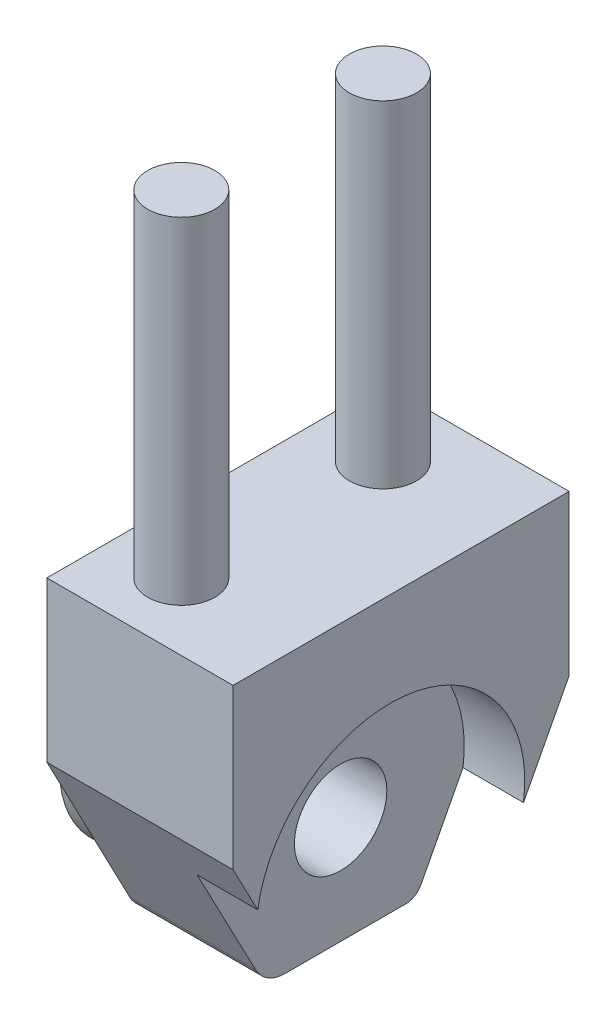
SolidWorks part; units mm, degrees
material "3.0205 (EN-AW 1200)"
ref_plane "Plan de face" through (0, 0, 0) normal (0, 0, 1) x (1, 0, 0)
ref_plane "Plan de dessus" through (0, 0, 0) normal (0, 1, 0) x (1, 0, 0)
ref_plane "Plan de droite" through (0, 0, 0) normal (1, 0, 0) x (0, 0, -1)
sketch "Esquisse1" plane through (0, 0, 0) normal (0, 1, 0) x (1, 0, 0)
  line L1 (15.8141, 19.6321) -> (37.9741, 19.6321)
  line L2 (15.8141, 19.6321) -> (15.8141, -20.3679)
  line L3 (15.8141, -20.3679) -> (37.9741, -20.3679)
  line L4 (37.9741, 19.6321) -> (37.9741, -20.3679)
  dimension "D1" = 40
  dimension "D2" = 22.16
extrude "Boss.-Extru.1" add sketch "Esquisse1" along normal blind 40
chamfer "Chanfrein1" distance 11 distance2 21 1 edges at (26.8941, 0, 20.3679) first distance on face at (26.8941, 0, 0.3679)
chamfer "Chanfrein2" distance 11 distance2 21 1 edges at (26.8941, 0, -19.6321) first distance on face at (26.8941, 0, -5.1321)
fillet "Congé1" radius 4 1 edges at (26.8941, 0, 9.3679)
sketch "Esquisse2" plane through (0, 40, 0) normal (0, 1, 0) x (1, 0, 0)
  line L1 (15.8141, 19.6321) -> (15.8141, -20.3679) construction
  line L2 (15.8141, -20.3679) -> (37.9741, -20.3679) construction
  line L4 (37.9741, 19.6321) -> (15.8141, 19.6321) construction
  circle A0 centre (23.8141, -12.3679) radius 4
  circle A1 centre (23.8141, 11.6321) radius 4
  dimension "D1" = 8
  dimension "D4" = 8
  dimension "D2" = 8
  dimension "D3" = 8
  dimension "D5" = 8
  dimension "D6" = 8
extrude "Boss.-Extru.2" add sketch "Esquisse2" along normal blind 40 contours A1
extrude "Boss.-Extru.3" add sketch "Esquisse2<3>" along normal blind 40
sketch "Esquisse2<3>" plane through (0, 40, 0) normal (0, 1, 0) x (1, 0, 0) same geometry as "Esquisse2"
sketch "Esquisse3" plane through (15.8141, 0, 0) normal (-1, 0, 0) x (0, 0, 1)
  line L0 (-8.6321, 0) -> (6.9476, 0) construction
  line L2 (-19.6321, 40) -> (-19.6321, 21) construction
  circle A0 centre (0.3679, 13.5) radius 12.5
  dimension "D1" = 25
  dimension "D2" = 13.5
  dimension "D3" = 20
extrude "Boss.-Extru.4" add sketch "Esquisse3" along normal blind 6
sketch "Esquisse4" plane through (37.9741, 0, 0) normal (1, 0, 0) x (0, 0, -1)
  line L0 (-20.3679, 40) -> (19.6321, 40) construction
  circle A0 centre (-1.6508, 12.8) radius 16
  dimension "D1" = 32
  dimension "D2" = 27.2
extrude "Enlèv. mat.-Extru.1" cut sketch "Esquisse4" against normal blind 7.2
sketch "Esquisse6" plane through (30.7741, 0, 0) normal (1, 0, 0) x (0, 0, -1)
  line L1 (0.8273, 4.7453) -> (12.9159, 4.7453)
  line L2 (0.8273, 4.7453) -> (0.8273, -2.9048)
  line L3 (0.8273, -2.9048) -> (12.9159, -2.9048)
  line L4 (12.9159, 4.7453) -> (12.9159, -2.9048)
extrude "Enlèv. mat.-Extru.2" cut sketch "Esquisse6" along normal through all
fillet "Congé2" radius 2 1 edges at (23.2941, 0, -8.6321)
sketch "Esquisse8" plane through (37.9741, 0, -37.9741) normal (-1, 0, 0) x (0, 0, 1)
  line L1 (58.342, 40) -> (18.342, 40) construction
  circle A0 centre (38.342, 12.8) radius 5.5
  dimension "D1" = 11
  dimension "D2" = 27.2
  dimension "D3" = 20
extrude "Enlèv. mat.-Extru.5" cut sketch "Esquisse8" along normal blind 15
